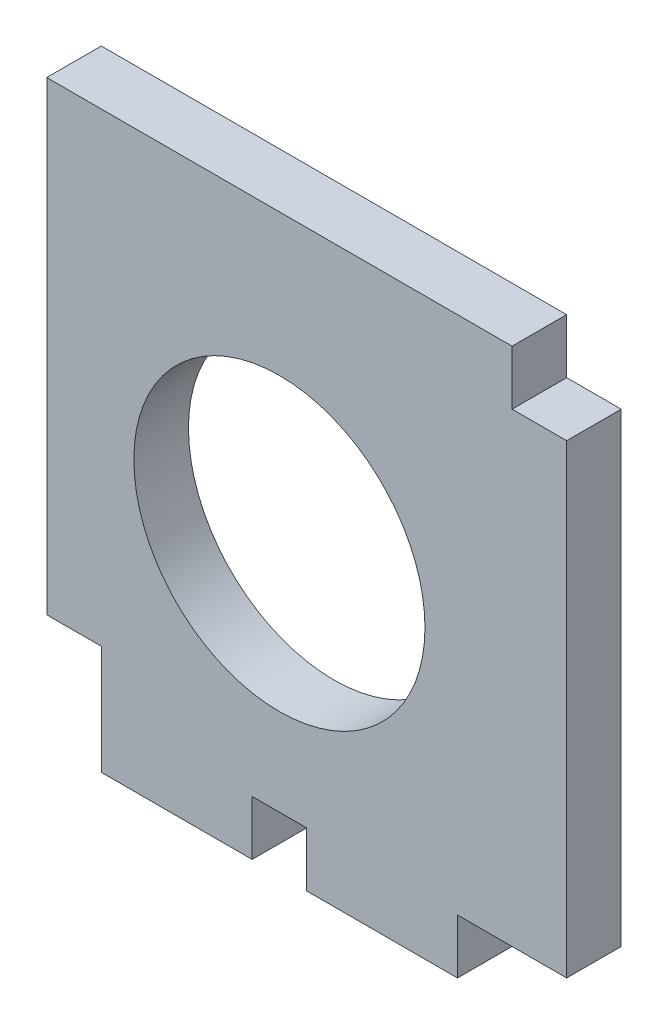
SolidWorks part; units mm, degrees
ref_plane "Front Plane" through (0, 0, 0) normal (0, 0, 1) x (1, 0, 0)
ref_plane "Top Plane" through (0, 0, 0) normal (0, 1, 0) x (1, 0, 0)
ref_plane "Right Plane" through (0, 0, 0) normal (1, 0, 0) x (0, 0, -1)
sketch "Sketch1" plane through (0, 0, 0) normal (0, 0, 1) x (1, 0, 0)
  line L0 (-20.3, -20.3) -> (-15.6929, -20.3) construction
  line L1 (-20.3, 34.9375) -> (-20.3, 54.9375) construction
  line L2 (20.3, -25.0625) -> (-20.3, -25.0625)
  line L3 (20.3, -25.0625) -> (20.3, 25.0625)
  line L4 (20.3, 25.0625) -> (-20.3, 25.0625)
  line L5 (-20.3, -25.0625) -> (-20.3, 25.0625)
  line L6 (-20.3, -20.3) -> (-15.5375, -20.3)
  line L7 (-20.3, -20.3) -> (-20.3, -15.5375)
  line L8 (20.3, -20.3) -> (20.3, 20.3) construction
  line L9 (-0.3, -25.0625) -> (19.7, -25.0625) construction
  line L10 (20.3, 20.3) -> (-20.3, 20.3) construction
  line L11 (-20.3, -20.3) -> (20.3, -20.3) construction
  line L12 (-20.3, -20.3) -> (20.3, -20.3)
  line L13 (-15.5375, -20.3) -> (-15.5375, -5.0625) construction
  line L14 (-20.3, -25.0625) -> (-15.5375, -25.0625)
  line L15 (-20.3, -25.0625) -> (-20.3, -20.3)
  line L16 (-20.3, -20.3) -> (-15.5375, -20.3)
  line L17 (-15.5375, -25.0625) -> (-15.5375, -20.3)
  line L18 (20.3, -25.0625) -> (15.5375, -25.0625)
  line L19 (20.3, -25.0625) -> (20.3, -20.3)
  line L20 (20.3, -20.3) -> (15.5375, -20.3)
  line L21 (15.5375, -25.0625) -> (15.5375, -20.3)
  line L22 (0, -25.0625) -> (0, -20.3) construction
  line L23 (15.6929, -20.3) -> (2.4051, -20.3) construction
  line L24 (-2.3812, -20.3) -> (2.3813, -20.3)
  line L25 (-2.3812, -20.3) -> (-2.3812, -25.0625)
  line L26 (-2.3812, -25.0625) -> (2.3813, -25.0625)
  line L27 (2.3813, -20.3) -> (2.3813, -25.0625)
  line L28 (-2.3812, -20.3) -> (2.3813, -25.0625) construction
  line L29 (-2.3812, -25.0625) -> (2.3813, -20.3) construction
  line L30 (20.3, 20.3) -> (25.0625, 20.3)
  line L31 (20.3, 20.3) -> (20.3, -20.3)
  line L32 (20.3, -20.3) -> (25.0625, -20.3)
  line L33 (25.0625, 20.3) -> (25.0625, -20.3)
  line L34 (-20.3, -15.5375) -> (-15.5375, -15.5375)
  line L35 (-15.5375, -20.3) -> (-15.5375, -15.5375)
  point P23 (0, -22.6812)
  dimension "D1" = 4.7625
  dimension "D2" = 4.7625
  dimension "D3" = 4.7625
  dimension "D4" = 4.7625
  dimension "D5" = 4.7625
extrude "Boss-Extrude1" add sketch "Sketch1" along normal blind 4.7625 contours L25 L12 L17 L2 | L12 L27 L2 L21 | L5 L12 L3 L4 | L31 L30 L33 L32 region at (8.9594, -22.6812, 0) region at (0.2234, 2.6344, 0) region at (-8.9594, -22.6812, 0)
sketch "Sketch2" plane through (0, 0, 4.7625) normal (0, 0, 1) x (1, 0, 0)
  circle A0 centre (0, 0) radius 12.7
  dimension "D1" = 25.4
extrude "Cut-Extrude1" cut sketch "Sketch2" against normal through all
